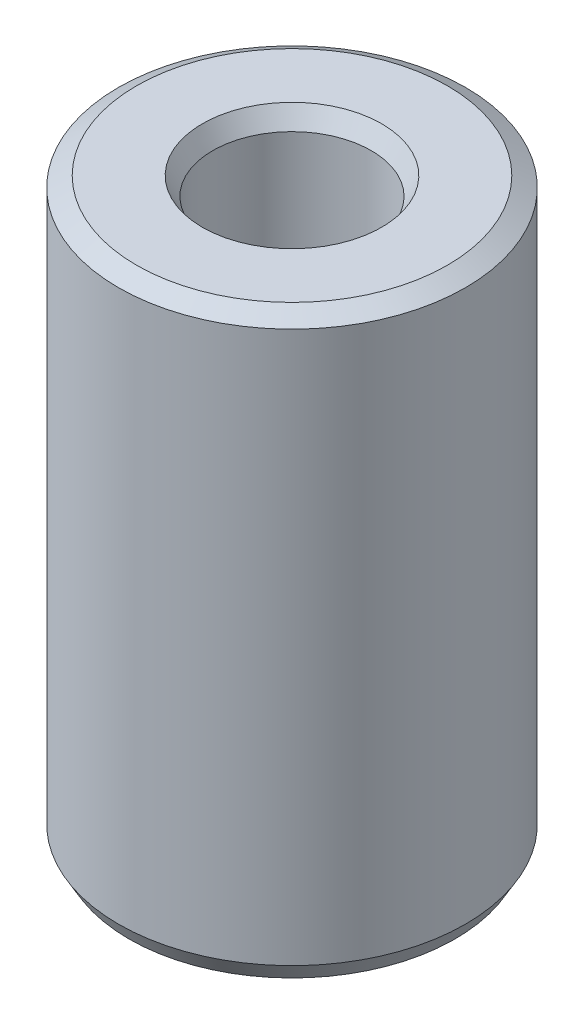
SolidWorks part; units mm, degrees
ref_plane "Front Plane" through (0, 0, 0) normal (0, 0, 1) x (1, 0, 0)
ref_plane "Top Plane" through (0, 0, 0) normal (0, 1, 0) x (1, 0, 0)
ref_plane "Right Plane" through (0, 0, 0) normal (1, 0, 0) x (0, 0, -1)
sketch "Sketch1" plane through (0, 0, 0) normal (0, 1, 0) x (1, 0, 0)
  circle A0 centre (0, 0) radius 40
  dimension "SLEEVE_OD" = 80
extrude "Boss-Extrude1" add sketch "Sketch1" along normal blind 133.6507
sketch "Sketch2" plane through (0, 0, 0) normal (0, 1, 0) x (1, 0, 0)
  circle A0 centre (0, 0) radius 18.2787
  dimension "BORE_D" = 36.5574
extrude "Cut-Extrude1" cut sketch "Sketch2" along normal through all
chamfer "Chamfer1" distance 2.4019 angle 60 4 edges at (0, 133.6507, 18.2787) (0, 0, 18.2787) (0, 0, 40) (0, 133.6507, 40) first distance on face at (0, 133.6507, 18.2787) first distance on face at (0, 0, 18.2787) first distance on face at (0, 133.6507, 40)
